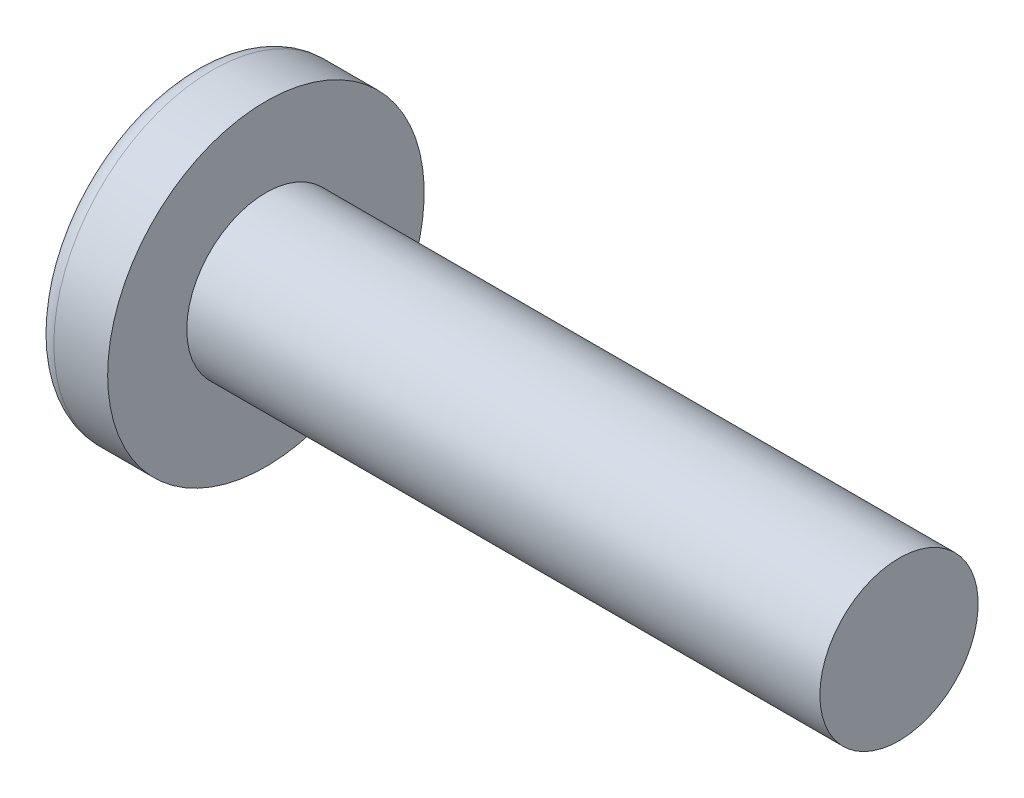
SolidWorks part; units mm, degrees
ref_plane "Plane1" through (0, 0, 0) normal (0, 0, 1) x (1, 0, 0)
ref_plane "Plane2" through (0, 0, 0) normal (0, 1, 0) x (1, 0, 0)
ref_plane "Plane3" through (0, 0, 0) normal (1, 0, 0) x (0, 0, -1)
sketch "BodySke" plane through (0, 0, 0) normal (0, 0, 1) x (1, 0, 0)
  line L0 (7.5, 5) -> (7.5, 10)
  line L1 (9, 6.35) -> (9, -3.175) construction
  line L2 (-25.4, 0) -> (127, 0) construction
  line L3 (47.5, 0) -> (0, 0)
  line L4 (7.5, 5) -> (47.5, 5)
  line L5 (47.5, 5) -> (47.5, 0)
  line L6 (4.1004, 10) -> (7.5, 10)
  line L7 (7.5, -5) -> (47.5, -5) construction
  line L8 (7.5, 6.35) -> (7.5, -3.175) construction
  arc A0 (3.1356, 9.5135) -> (0, 0) centre (16, 0) ccw
  arc A2 (3.1356, 9.5135) -> (4.1004, 10) centre (4.1004, 8.8) cw
  dimension "Head_fillet_rad" = 1.2
  dimension "Length" = 40
  dimension "Head_ht" = 7.5
  dimension "Head_dia" = 20
  dimension "Diameter" = 10
revolve "Base-Revolve" add sketch "BodySke" angle 360 about L2
cosmetic thread "ThreadCosmetic" [suppressed] parameters "Thread_length"=38.5, "Thread_minor"=8.344
sketch "Sketch3" plane through (0, 0, 0) normal (1, 0, 0) x (0, 0, -1)
  line L0 (0.92, -5.09) -> (-0.92, -5.09)
  line L1 (0.92, -5.09) -> (0.92, 5.09)
  line L2 (-0.92, 5.09) -> (0.92, 5.09)
  line L3 (-0.92, 5.09) -> (-0.92, -5.09)
  dimension "D1" = 5.09
  dimension "D2" = 0.92
ref_plane "Plane4" through (6.09, 0, 0) normal (1, 0, 0) x (0, 0, -1)
sketch "Sketch4" plane through (6.09, 0, 0) normal (1, 0, 0) x (0, 0, -1)
  line L0 (0.46, -0.46) -> (-0.46, -0.46)
  line L1 (0.46, -0.46) -> (0.46, 0.46)
  line L2 (-0.46, 0.46) -> (0.46, 0.46)
  line L3 (-0.46, 0.46) -> (-0.46, -0.46)
  dimension "D2" = 0.92
  dimension "D1" = 0.92
  dimension "D3" = 0.46
  dimension "D4" = 0.46
loft "Cut-Loft1" cut profiles "Sketch3", "Sketch4"
pattern_circular "CirPattern1" count 2 every 90 about axis through (-25.4, 0, 0) along (1, 0, 0) of "Cut-Loft1"
sketch "ThdSchSke" plane through (0, 0, 0) normal (0, 0, 1) x (1, 0, 0)
  line L0 (9, -4.172) -> (8.4202, -5)
  line L1 (9, -4.172) -> (9.5798, -5)
  line L2 (9.5798, -5) -> (9.5798, -6.25)
  line L3 (-3.175, 0) -> (5.1513, 0) construction
  line L5 (9.5798, -6.25) -> (8.4202, -6.25)
  line L6 (8.4202, -6.25) -> (8.4202, -5)
  dimension "Thread_minor" = 8.344
  dimension "Diameter" = 10
  dimension "Start" = 9
revolve "ThreadSchematic" [suppressed] cut sketch "ThdSchSke" angle 360 about L3
pattern_linear "ThdSchPat" [suppressed]
equation "\"D1@Sketch3\" = \"Cross_dia@Sketch3\" / 2"
equation "\"D2@Sketch3\" = \"Cross_width@Sketch3\" / 2"
equation "\"D1@Sketch4\" = \"Cross_width@Sketch3\" *.5"
equation "\"D2@Sketch4\" = \"D1@Sketch4\""
equation "\"D3@Sketch4\" = \"D1@Sketch4\" / 2"
equation "\"D4@Sketch4\" = \"D2@Sketch4\" / 2"
equation "\"Thread_length@ThreadCosmetic\" = ((sgn( (\"Length@BodySke\" - \"Advance@BodySke\" ) - \"Thread_nom@BodySke\" )-1)*( (\"Length@BodySke\" - \"Advance@BodySke\" ) - \"Thread_nom@BodySke\" ))/-2+ \"Thread_nom@BodySke\""
equation "\"Thread_minor@ThdSchSke\" = \"Thread_minor@ThreadCosmetic\""
equation "\"Diameter@ThdSchSke\" = \"Diameter@BodySke\""
equation "\"Overcut@ThdSchSke\" = \"Diameter@BodySke\" * 1.25"
equation "\"Start@ThdSchSke\" = \"Head_ht@BodySke\" + \"Length@BodySke\" - \"Thread_length@ThreadCosmetic\"  '---Non-countersunk---"
equation "\"Num_threads@ThdSchPat\" = int( \"Thread_length@ThreadCosmetic\" / \"Advance@BodySke\" + 0.999 )  + 1"
equation "\"Advance@ThdSchPat\" = \"Thread_length@ThreadCosmetic\" /  (\"Num_threads@ThdSchPat\" - 1) 'relax it"
